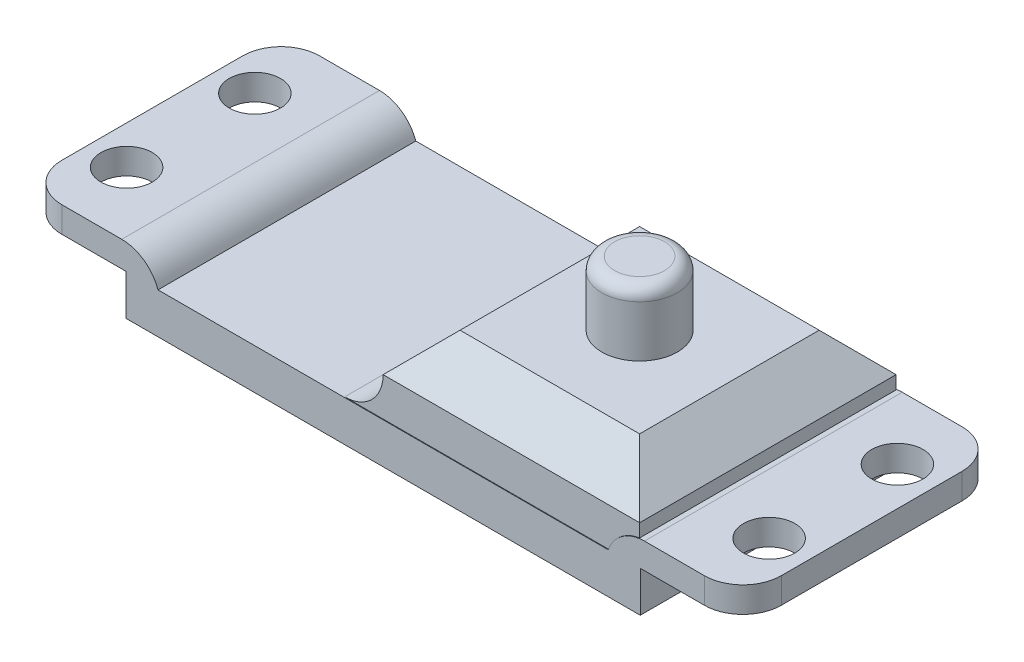
SolidWorks part; units mm, degrees
ref_plane "Front Plane" through (0, 0, 0) normal (0, 0, 1) x (1, 0, 0)
ref_plane "Top Plane" through (0, 0, 0) normal (0, 1, 0) x (1, 0, 0)
ref_plane "Right Plane" through (0, 0, 0) normal (1, 0, 0) x (0, 0, -1)
sketch "Sketch1" plane through (0, 0, 0) normal (0, 1, 0) x (1, 0, 0)
  line L1 (-20.05, -10.05) -> (20.05, -10.05)
  line L2 (-20.05, -10.05) -> (-20.05, 10.05)
  line L3 (-20.05, 10.05) -> (20.05, 10.05)
  line L4 (20.05, -10.05) -> (20.05, 10.05)
  line L5 (-20.05, -10.05) -> (20.05, 10.05) construction
  line L6 (-20.05, 10.05) -> (20.05, -10.05) construction
  point P0 (0, 0)
  dimension "D1" = 40.1
  dimension "D2" = 20.1
extrude "Boss-Extrude1" add sketch "Sketch1" along normal blind 3.175
sketch "Sketch2" plane through (0, 3.175, 0) normal (0, 1, 0) x (1, 0, 0)
  line L0 (-20.05, -10.05) -> (20.05, -10.05) construction
  line L1 (20.05, 10.05) -> (17.55, 10.05)
  line L2 (20.05, 10.05) -> (20.05, -10.05)
  line L3 (20.05, -10.05) -> (17.55, -10.05)
  line L4 (17.55, 10.05) -> (17.55, -10.05)
  dimension "D1" = 2.5
extrude "Boss-Extrude2" add sketch "Sketch2" along normal blind 2
sketch "Sketch3" plane through (20.05, 0, 0) normal (1, 0, 0) x (0, 0, -1)
  line L0 (10.05, 5.175) -> (10.05, 0) construction
  line L1 (-10.05, 5.175) -> (10.05, 5.175)
  line L2 (-10.05, 5.175) -> (-10.05, 3.175)
  line L3 (-10.05, 3.175) -> (10.05, 3.175)
  line L4 (10.05, 5.175) -> (10.05, 3.175)
  line L5 (10.05, 5.175) -> (10.05, 3.175) construction
extrude "Boss-Extrude3" add sketch "Sketch3" along normal blind 8
sketch "Sketch4" plane through (0, 3.175, 0) normal (0, -1, 0) x (1, 0, 0)
  line L0 (25.05, 5) -> (25.05, -5) construction
  line L1 (1.7463, 0) -> (-1.7463, 0) construction
  line L2 (20.05, 10.05) -> (20.05, -10.05) construction
  circle A0 centre (25.05, 5) radius 2
  circle A1 centre (25.05, -5) radius 2
  point P4 (25.05, 0)
  dimension "D1" = 4
  dimension "D2" = 10
  dimension "D3" = 5
extrude "Cut-Extrude1" cut sketch "Sketch4" against normal through all both and the other way through all
fillet "Fillet1" radius 3 1 edges at (17.55, 5.175, 0)
fillet "Fillet2" radius 3 2 edges at (28.05, 4.175, -10.05) (28.05, 4.175, 10.05)
mirror "Mirror2" about plane through (0, 0, 0) normal (1, 0, 0) of "Fillet2", "Fillet1", "Cut-Extrude1", "Boss-Extrude3", "Boss-Extrude2"
sketch "Sketch7" plane through (0, 3.175, 0) normal (0, 1, 0) x (1, 0, 0)
  line L1 (-0.05, 10) -> (19.95, 10)
  line L2 (-0.05, 10) -> (-0.05, -10)
  line L3 (-0.05, -10) -> (19.95, -10)
  line L4 (19.95, 10) -> (19.95, -10)
  line L5 (-0.05, 10) -> (19.95, -10) construction
  line L6 (-0.05, -10) -> (19.95, 10) construction
  circle A0 centre (25.05, -5) radius 2 construction
  point P0 (9.95, 0)
  dimension "D1" = 15.1
  dimension "D2" = 20
  dimension "D3" = 20
extrude "Boss-Extrude5" add sketch "Sketch7" along normal blind 6
sketch "Sketch5" plane through (0, 9.175, 0) normal (0, 1, 0) x (1, 0, 0)
  circle A0 centre (9.95, 0) radius 2.95
  circle A1 centre (25.05, -5) radius 2 construction
  dimension "D1" = 5.9
  dimension "D2" = 15.1
extrude "Boss-Extrude4" add sketch "Sketch5" along normal blind 5
fillet "Fillet4" radius 3 1 edges at (-0.05, 3.175, 0)
chamfer "Chamfer1" distance 3 angle 45 4 edges at (19.95, 9.175, 0) (9.95, 9.175, -10) (-0.05, 9.175, 0) (9.95, 9.175, 10)
fillet "Fillet5" radius 1 1 edges at (9.95, 14.175, 2.95)
